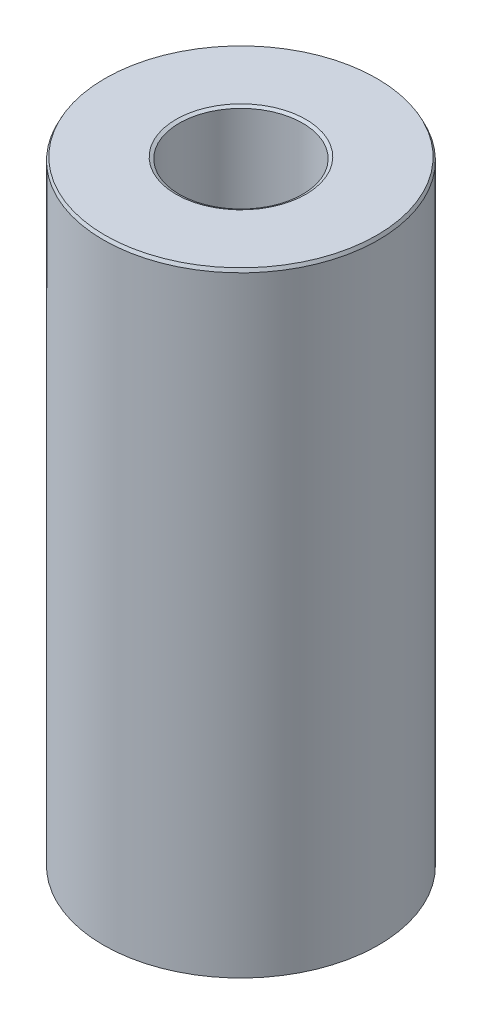
SolidWorks part; units mm, degrees
ref_plane "Front Plane" through (0, 0, 0) normal (0, 0, 1) x (1, 0, 0)
ref_plane "Top Plane" through (0, 0, 0) normal (0, 1, 0) x (1, 0, 0)
ref_plane "Right Plane" through (0, 0, 0) normal (1, 0, 0) x (0, 0, -1)
sketch "Sketch1" plane through (0, 0, 0) normal (0, 1, 0) x (1, 0, 0)
  circle A0 centre (0, 0) radius 12.5
  dimension "SLEEVE_OD" = 25
extrude "Boss-Extrude1" add sketch "Sketch1" along normal blind 55.955
sketch "Sketch2" plane through (0, 0, 0) normal (0, 1, 0) x (1, 0, 0)
  circle A0 centre (0, 0) radius 5.6074
  dimension "BORE_D" = 11.2147
extrude "Cut-Extrude1" cut sketch "Sketch2" along normal through all
chamfer "Chamfer1" distance 0.2953 angle 26.532 4 edges at (0, 55.955, 5.6074) (0, 0, 5.6074) (0, 0, 12.5) (0, 55.955, 12.5) first distance on face at (0, 55.955, 5.6074) first distance on face at (0, 0, 5.6074) first distance on face at (0, 55.955, 12.5)
